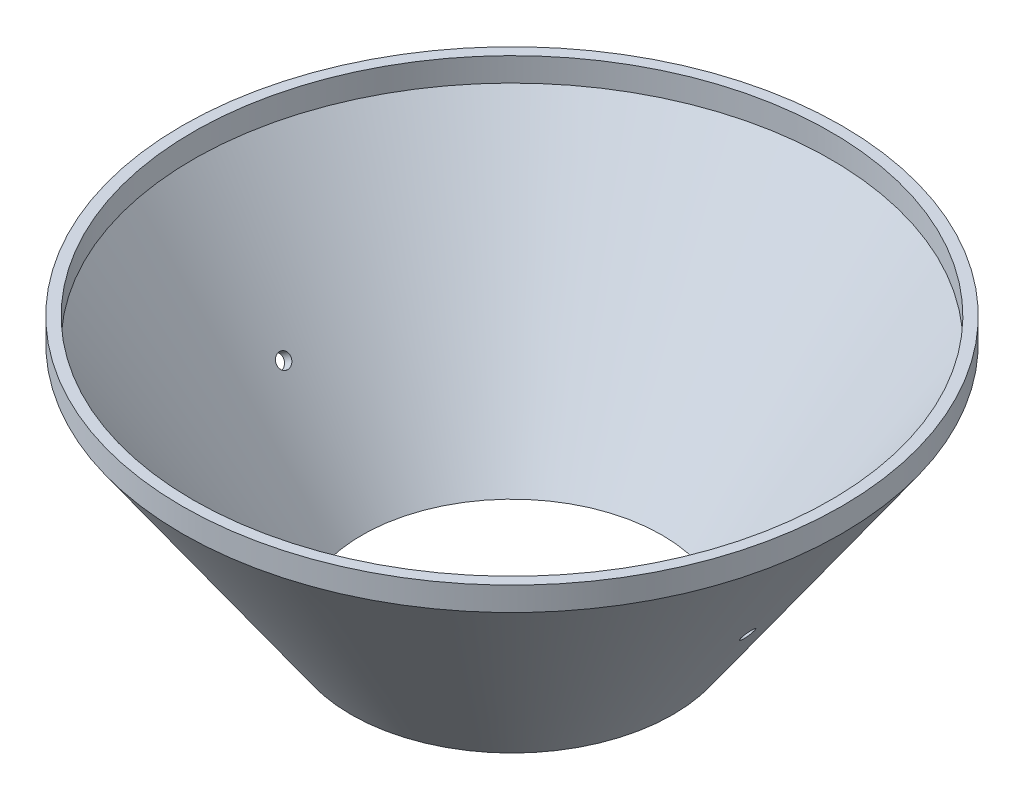
SolidWorks part; units mm, degrees
ref_plane "Front Plane" through (0, 0, 0) normal (0, 0, 1) x (1, 0, 0)
ref_plane "Top Plane" through (0, 0, 0) normal (0, 1, 0) x (1, 0, 0)
ref_plane "Right Plane" through (0, 0, 0) normal (1, 0, 0) x (0, 0, -1)
sketch "Sketch35" plane through (0, 0, 0) normal (0, 0, 1) x (1, 0, 0)
  line L0 (0, 0) -> (12.63, 0)
  line L1 (55, 0) -> (-55, 0) construction
  line L2 (12.63, 0) -> (26.8344, 20.286)
  line L3 (26.8344, 20.286) -> (0, 20.286)
  line L4 (0, -55) -> (0, 55) construction
  line L5 (0, 20.286) -> (0, 0)
  line L6 (0, 0) -> (13.5456, 0)
  line L7 (13.5456, 0) -> (27.75, 20.286)
  line L8 (27.75, 20.286) -> (0, 20.286)
  line L9 (19.2261, 9.4202) -> (19.8405, 8.9901) construction
  point P5 (19.2261, 9.4202)
  dimension "D1" = 125
  dimension "D2" = 12.63
  dimension "D3" = 27.75
  dimension "D4" = 0.75
  dimension "D5" = 11.5
revolve "Revolve1" add sketch "Sketch35" angle 360 about L5 region at (16.3076, 4.6034, 0) region at (23.4152, 14.7449, 0)
ref_plane "Plane2" through (8.4749, -5.9342, 0) normal (-0.8192, 0.5736, 0) x (0, 0, 1)
sketch "Sketch36" plane through (8.4749, -5.9342, 0) normal (-0.8192, 0.5736, 0) x (0, 0, 1)
  circle A0 centre (0, 18.7443) radius 0.6
  point P8 (0, 7.2443)
extrude "side-holes" cut sketch "Sketch36" against normal blind 2 and the other way blind 2 contours A0
pattern_circular "CirPattern2" count 2 over 360 about axis through (0, 0, 0) along (0, 1, 0) of "side-holes"
sketch "Sketch37" plane through (0, 20.286, 0) normal (0, 1, 0) x (1, 0, 0)
  circle A0 centre (0, 0) radius 26.8344
  circle A1 centre (0, 0) radius 27.75
  circle A2 centre (0, 0) radius 26.8344 construction
  circle A3 centre (0, 0) radius 27.75 construction
extrude "Boss-Extrude1" add sketch "Sketch37" along normal blind 2
